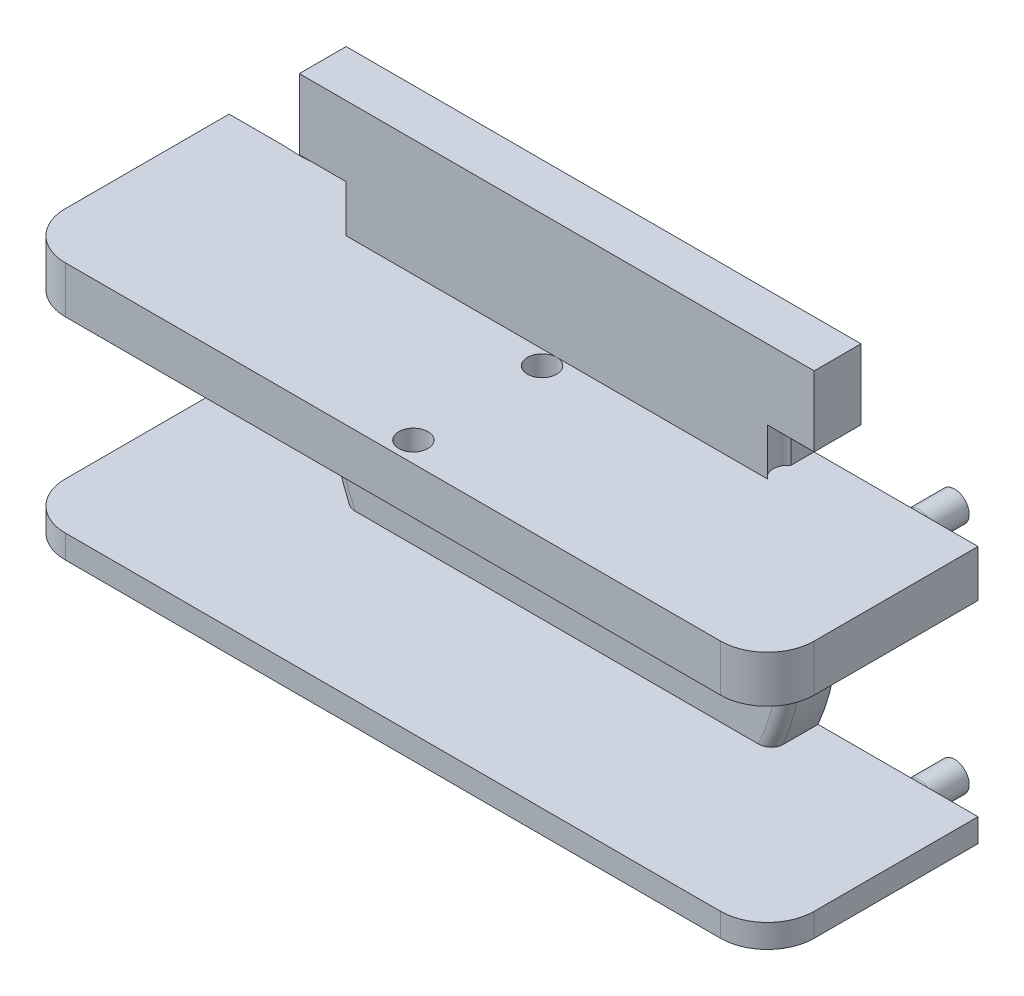
SolidWorks part; units mm, degrees
material "UNOBTANIUM"
ref_plane "Top Plane" through (0, 0, 0) normal (0, 0, 1) x (1, 0, 0)
ref_plane "Right Plane" through (0, 0, 0) normal (0, 1, 0) x (1, 0, 0)
ref_plane "Front Plane" through (0, 0, 0) normal (1, 0, 0) x (0, 0, -1)
ref_axis "x-axis" through (-17.6, 0, 0) along (1, 0, 0)
ref_axis "y-axis" through (0, -9.7375, 0) along (0, 1, 0)
ref_axis "z-axis" through (0, 0, 8.775) along (0, 0, -1)
sketch "Sketch1" plane through (0, 0, 0) normal (0, 0, 1) x (1, 0, 0)
  line L0 (-11, 6) -> (-11, 11)
  line L1 (-11, -6) -> (11, -6)
  line L2 (-11, -6) -> (-11, 6)
  line L3 (-11, 6) -> (11, 6) construction
  line L4 (11, -6) -> (11, 6)
  line L5 (-11, -6) -> (11, 6) construction
  line L6 (-11, 6) -> (11, -6) construction
  line L7 (-11, 11) -> (11, 11)
  line L8 (11, 11) -> (11, 6)
  circle A0 centre (0, 0) radius 9.25 construction
  point P0 (0, 0)
  dimension "D1" = 18.5
  dimension "D2" = 22
  dimension "D3" = 12
  dimension "D4" = 5
extrude "Boss-Extrude1" add sketch "Sketch1" along normal blind 2
sketch "Sketch2" plane through (0, 0, 2) normal (0, 0, -1) x (-1, 0, 0)
  circle A0 centre (0, 0) radius 1.575
  dimension "D1" = 3.15
extrude "Boss-Extrude2" add sketch "Sketch2" along normal blind 4 separate body
sketch "Sketch3" plane through (0, 0, 0) normal (0, 0, -1) x (-1, 0, 0)
  line L0 (11, -6) -> (-11, 6) construction
  circle A0 centre (0, 0) radius 3.5
  dimension "D1" = 7
extrude "Boss-Extrude3" add sketch "Sketch3" along normal blind 1
sketch "Sketch4" plane through (0, 0, 0) normal (0, 0, -1) x (-1, 0, 0)
  line L0 (11, -6) -> (-11, -6) construction
  line L1 (11, 11) -> (9, 11)
  line L2 (11, 11) -> (11, -6)
  line L3 (11, -6) -> (9, -6)
  line L4 (9, 11) -> (9, -6)
  line L5 (0, -6) -> (0, 11) construction
  line L7 (-9, 11) -> (-9, -6)
  line L8 (-11, -6) -> (-9, -6)
  line L9 (-11, 11) -> (-11, -6)
  line L10 (-11, 11) -> (-9, 11)
  line L11 (11, 11) -> (-11, 11) construction
  dimension "D1" = 2
extrude "Boss-Extrude4" add sketch "Sketch4" along normal blind 0.001
sketch "Sketch5" plane through (0, 0, 0) normal (0, 0, -1) x (-1, 0, 0)
  line L0 (-9, -6) -> (-9, 11) construction
  line L1 (9, 11) -> (-9, 11)
  line L2 (9, 11) -> (9, 9)
  line L3 (9, 9) -> (-9, 9)
  line L4 (-9, 11) -> (-9, 9)
  dimension "D1" = 2
extrude "Boss-Extrude5" add sketch "Sketch5" along normal up to surface (0.001 mm away) up to face at (-10, 2.5, -0.001)
sketch "Sketch6" plane through (11, 0, 0) normal (1, 0, 0) x (0, 0, -1)
  line L0 (-2, -6) -> (-2, 11) construction
  line L1 (0.001, -6) -> (-2, -6)
  line L2 (0.001, -6) -> (0.001, -4)
  line L3 (0.001, -4) -> (-2, -4)
  line L4 (-2, -6) -> (-2, -4)
  line L6 (0.001, 11) -> (0.001, -6) construction
  line L7 (-2, 6) -> (0.001, 6)
  line L8 (-2, 6) -> (-2, 4)
  line L9 (-2, 4) -> (0.001, 4)
  line L10 (0.001, 6) -> (0.001, 4)
  dimension "D1" = 2
extrude "Boss-Extrude6" add sketch "Sketch6" along normal blind 5
mirror "Mirror1" about plane through (0, 0, 0) normal (1, 0, 0) of "Boss-Extrude6"
sketch "Sketch7" plane through (0, 0, -0.001) normal (0, 0, -1) x (-1, 0, 0)
  line L0 (-9, -6) -> (-9, 9) construction
  line L1 (-9, 0) -> (-9, 9)
  line L2 (-9, 9) -> (0, 9)
  line L3 (-9, 0) -> (-9, -6)
  line L4 (-9, -6) -> (-6.7082, -6)
  line L5 (11, -6) -> (-11, -6) construction
  arc A0 (0, 9) -> (-6.7082, -6) centre (0, 0) ccw
  line M18 (-9, -6) -> (-9, 9)
  line M19 (-9, 9) -> (9, 9)
extrude "Boss-Extrude7" add sketch "Sketch7" against normal up to surface (0.001 mm away) contours A0 L4 M18 | A0 M19 M18 region at (8.3306, -4.5409, -0.001) region at (6.9897, 6.9897, -0.001) up to face at (3.5, 0, 0)
sketch "Sketch8" plane through (0, 0, -0.001) normal (0, 0, -1) x (-1, 0, 0)
  line L0 (-11, 4) -> (-9.1652, 4)
  line L1 (-11, 4) -> (-11, -4)
  line L2 (-11, -4) -> (-9.1652, -4)
  arc A1 (-9.1652, 4) -> (-9.1652, -4) centre (0, 0) ccw
  dimension "D1" = 10
extrude "Cut-Extrude1" cut sketch "Sketch8" against normal through all
sketch "Sketch9" plane through (0, 0, -0.001) normal (0, 0, -1) x (-1, 0, 0)
  line L0 (-16, -4) -> (-9.1652, -4) construction
  line L1 (-8.0623, 4) -> (-11, 4)
  line L2 (-8.0623, 4) -> (-8.0623, -4)
  line L3 (-8.0623, -4) -> (-11, -4)
  line L4 (-11, 4) -> (-11, -4)
  line L5 (-11, -6) -> (-11, 6) construction
  arc A0 (0, 9) -> (-6.7082, -6) centre (0, 0) ccw construction
  arc A1 (0, 9) -> (-6.7082, -6) centre (0, 0) ccw construction
extrude "Cut-Extrude2" cut sketch "Sketch9" against normal up to surface (0.001 mm away) up to face at (3.5, 0, 0)
mirror "Mirror2" about plane through (0, 0, 0) normal (1, 0, 0) of "Cut-Extrude2", "Boss-Extrude7", "Cut-Extrude1"
sketch "Sketch21" plane through (0, 0, -0.001) normal (0, 0, -1) x (-1, 0, 0)
  circle A0 centre (0, 0) radius 9.75
  circle A1 centre (0, 0) radius 9 construction
  circle A2 centre (0, 0) radius 3.5 construction
  circle A3 centre (0, 0) radius 3.5
  dimension "D1" = 0.75
extrude "Cut-Extrude11" cut sketch "Sketch21" against normal up to surface (0.001 mm away) up to face at (0, -0.7091, 0)
sketch "Sketch10" plane through (0, 0, 2) normal (0, 0, 1) x (1, 0, 0)
  line L0 (-16, -4) -> (-16, -6) construction
  line L1 (16, -6) -> (-16, -6)
  line L2 (16, -6) -> (16, -4)
  line L3 (16, -4) -> (-16, -4)
  line L4 (-16, -6) -> (-16, -4)
  line L5 (-16, -4) -> (-9.1652, -4) construction
  line L7 (-16, 6) -> (16, 6)
  line L8 (-16, 6) -> (-16, 4)
  line L9 (-16, 4) -> (16, 4)
  line L10 (16, 6) -> (16, 4)
extrude "Boss-Extrude8" add sketch "Sketch10" along normal blind 7
fillet "Fillet1" radius 0.5 2 edges at (10, 0, 2) (-10, 0, 2)
sketch "Sketch11" plane through (0, 0, -0.001) normal (0, 0, -1) x (-1, 0, 0)
  line L0 (-16, -5) -> (-13, -5) construction
  line L1 (-16, -6) -> (-16, -4) construction
  circle A0 centre (-13, -5) radius 0.625
  dimension "D1" = 1.25
  dimension "D2" = 3
extrude "Boss-Extrude9" add sketch "Sketch11" along normal blind 2
sketch "Sketch14" plane through (0, 0, -0.001) normal (0, 0, -1) x (-1, 0, 0)
  line L1 (11, 6) -> (9, 6)
  line L2 (11, 6) -> (11, 8)
  line L3 (11, 8) -> (9, 8)
  line L4 (9, 6) -> (9, 8)
  line L5 (-11, 6) -> (-9, 6)
  line L6 (-11, 6) -> (-11, 8)
  line L7 (-11, 8) -> (-9, 8)
  line L8 (-9, 6) -> (-9, 8)
  dimension "D1" = 18
  dimension "D2" = 2
extrude "Cut-Extrude5" cut sketch "Sketch14" against normal through all
sketch "Sketch12" plane through (0, 0, -0.001) normal (0, 0, -1) x (-1, 0, 0)
  line L0 (-16, -5) -> (-13, -5) construction
  line L1 (-16, -6) -> (-16, -4) construction
  line L3 (16, -5) -> (13, -5) construction
  line L4 (16, -6) -> (16, -4) construction
  circle A0 centre (13, -5) radius 0.675
  circle A1 centre (-13, -5) radius 0.625 construction
  circle A2 centre (-13, -5) radius 0.625 construction
  dimension "D1" = 1.35
  dimension "D2" = 1.25
extrude "Cut-Extrude3" cut sketch "Sketch12" against normal blind 2.5
sketch "Sketch16" plane through (0, 6, 0) normal (0, 1, 0) x (1, 0, 0)
  line L0 (-9, -2) -> (-9, 0.001) construction
  line L1 (-9, -1) -> (-9, -2)
  arc A1 (-9, -1) -> (-9, -2) centre (-9.375, -1.5) cw
  dimension "D1" = 0.25
  dimension "D2" = 1
extrude "Cut-Extrude6" cut sketch "Sketch16" along normal blind 2
mirror "Mirror3" about plane through (0, 0, 0) normal (0, 1, 0) of "Boss-Extrude9", "Cut-Extrude3"
mirror "Mirror4" about plane through (0, 0, 0) normal (1, 0, 0) of "Cut-Extrude6"
fillet "Fillet2" radius 0.5 2 edges at (12.375, 5, -0.001) (13.625, -5, -0.001)
fillet "Fillet3" radius 0.5 2 edges at (-13.675, 5, -0.001) (-13.675, -5, -0.001)
fillet "Fillet4" radius 2 4 edges at (16, -5, 9) (16, 5, 9) (-16, -5, 9) (-16, 5, 9)
sketch "Sketch17" plane through (0, -6, 0) normal (0, -1, 0) x (1, 0, 0)
  line L0 (-16, 7) -> (-16, -0.001) construction
  line L1 (-14, 9) -> (14, 9) construction
  line L2 (16, 7) -> (16, -0.001) construction
  line L3 (-16, 7) -> (-16, -0.001)
  line L4 (-14, 9) -> (14, 9)
  line L5 (16, 7) -> (16, -0.001)
  line L6 (14.5, 7) -> (14.5, -0.001)
  line L8 (-14, 7.5) -> (14, 7.5)
  line L9 (-14.5, 7) -> (-14.5, -0.001)
  line L10 (14.5, -0.001) -> (16, -0.001)
  line L11 (-14.5, -0.001) -> (-16, -0.001)
  arc A0 (-14, 9) -> (-16, 7) centre (-14, 7) ccw construction
  arc A1 (16, 7) -> (14, 9) centre (14, 7) ccw construction
  arc A2 (-14, 9) -> (-16, 7) centre (-14, 7) ccw
  arc A3 (16, 7) -> (14, 9) centre (14, 7) ccw
  arc A4 (14.5, 7) -> (14, 7.5) centre (14, 7) ccw
  arc A5 (-14, 7.5) -> (-14.5, 7) centre (-14, 7) ccw
  dimension "D1" = 1.5
extrude "Cut-Extrude7" cut sketch "Sketch17" against normal blind 1 and the other way through all
sketch "Sketch19" plane through (0, 6, 0) normal (0, 1, 0) x (1, 0, 0)
  line L0 (9, -2) -> (-9, -2) construction
  line L1 (0, -2.625) -> (0, -2) construction
  line L2 (9, -2) -> (-9, -2) construction
  circle A0 centre (0, -2.625) radius 0.625
  circle A1 centre (0, -8.125) radius 0.625
  point P4 (0, -2)
  dimension "D1" = 1.25
  dimension "D2" = 5.5
extrude "Cut-Extrude9" cut sketch "Sketch19" against normal up to surface (2 mm away) up to face at (0.0154, 4, 1.9997)
sketch "Sketch20" plane through (0, 0, -0.001) normal (0, 0, -1) x (-1, 0, 0)
  line L0 (-9, 8) -> (-11, 8) construction
  line L1 (-11, 11) -> (-9, 11)
  line L2 (-11, 11) -> (-11, 8)
  line L3 (-11, 8) -> (-9, 8)
  line L4 (-9, 11) -> (-9, 8)
  line L5 (11, 11) -> (-11, 11) construction
  line L6 (11, 8) -> (9, 8)
  line L7 (11, 8) -> (11, 11)
  line L8 (11, 11) -> (9, 11)
  line L9 (9, 8) -> (9, 11)
  dimension "D1" = 2
combine bodies "Combine2" operation type subtract main body 122 bodies to subtract 102
equation "\"D1@Sketch12\"=\"D2@Sketch12\"+.1"
